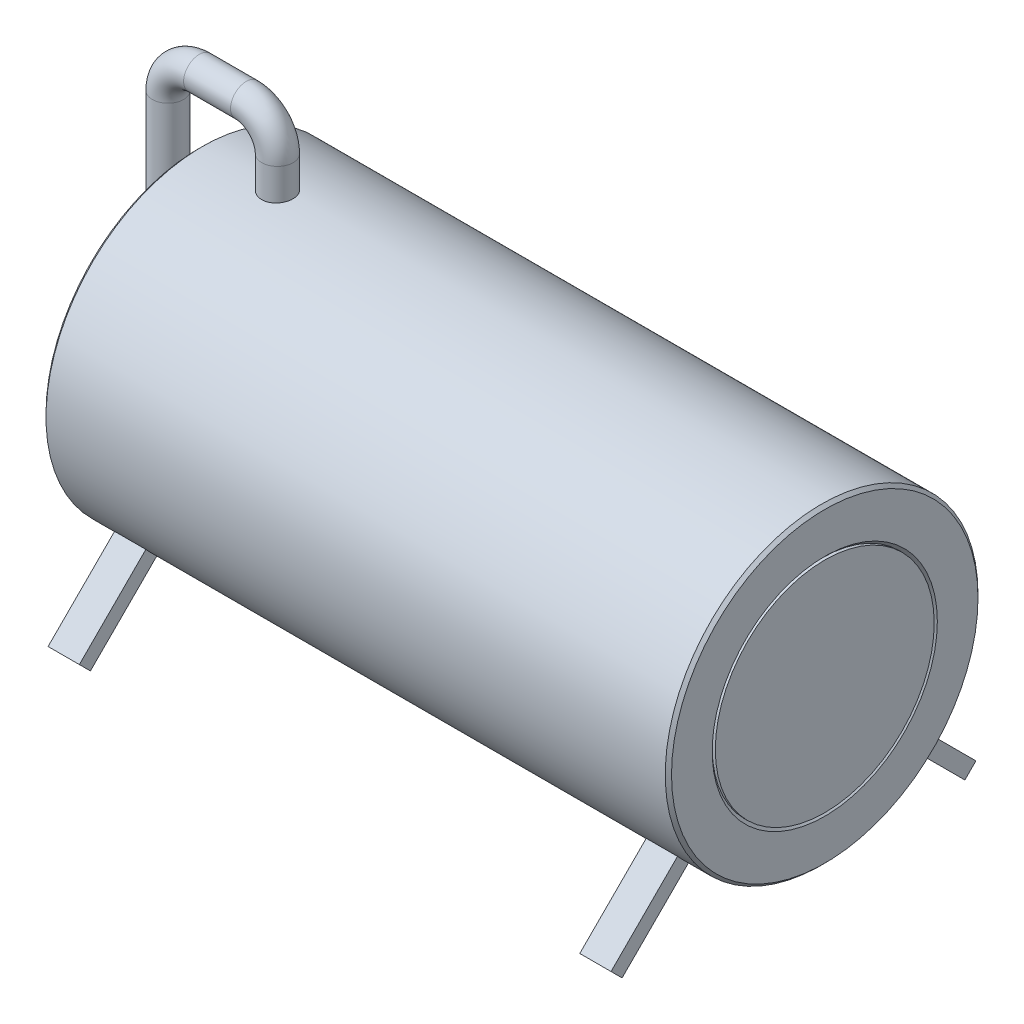
SolidWorks part; units mm, degrees
material "Aço galvanizado"
ref_plane "Plano frontal"
ref_plane "Plano superior" through (0, 0, 0) normal (0, 1, 0) x (1, 0, 0)
ref_plane "Plano direito" through (0, 0, 0) normal (1, 0, 0) x (0, 0, -1)
sketch "Esboço1" plane through (0, 0, 0) normal (1, 0, 0) x (0, 0, -1)
  circle A0 centre (0, 0) radius 50
  dimension "D1" = 100
extrude "Ressalto-extrusão1" add sketch "Esboço1" along normal blind 200
sketch "Esboço2" plane through (200, 0, 0) normal (1, 0, 0) x (0, 0, -1)
  circle A0 centre (0, 0) radius 35
  dimension "D1" = 70
extrude "Corte-extrusão1" cut sketch "Esboço2" against normal blind 200
sketch "Esboço3" plane through (0, 0, 0) normal (0, 0, 1) x (1, 0, 0)
  line L0 (200, 0) -> (0, 0) construction
  line L1 (200, -50) -> (200, 50) construction
  line L2 (0, 50) -> (0, -50) construction
  line L3 (5, 47.5) -> (195, 47.5)
  line L4 (5, 47.5) -> (5, 37.5)
  line L5 (5, 37.5) -> (195, 37.5)
  line L6 (195, 47.5) -> (195, 37.5)
  dimension "D1" = 75
  dimension "D2" = 95
  dimension "D3" = 5
  dimension "D4" = 5
revolve "Corte-Revolução1" cut sketch "Esboço3" angle 360 about L0
chamfer "Chanfro1" distance 1 angle 45 4 edges at (200, 0, -35) (200, 0, -50) (0, 0, -35) (0, 0, -50)
ref_plane "Plano1" through (10, 0, 0) normal (-1, 0, 0) x (0, 0, 1)
sketch "Esboço4" plane through (10, 0, 0) normal (-1, 0, 0) x (0, 0, 1)
  line L0 (0, 0) -> (0, -50) construction
  line L1 (0, 0) -> (-35.3553, -35.3553) construction
  line L2 (-37.0789, -33.5434) -> (-58.3363, -54.8008)
  line L3 (-58.3363, -54.8008) -> (-54.8008, -58.3363)
  line L4 (-54.8008, -58.3363) -> (-33.5434, -37.0789)
  circle A0 centre (0, 0) radius 50 construction
  arc A1 (-37.0789, -33.5434) -> (-33.5434, -37.0789) centre (0, 0) ccw
  dimension "D1" = 45
  dimension "D2" = 30
  dimension "D3" = 5
  dimension "D4" = 2.5
extrude "Ressalto-extrusão2" add sketch "Esboço4" against normal blind 10
ref_point "Ponto1"
ref_point "Ponto2"
ref_axis "Eixo1" through (200, 0, 0) along (-1, 0, 0)
pattern_circular "PadrãoCircular1" count 2 every 90 about axis through (200, 0, 0) along (-1, 0, 0) of "Ressalto-extrusão2"
pattern_linear "Padrão linear1" count 2 spacing 170 along (1, 0, 0) of "PadrãoCircular1"
ref_plane "Plano2" through (0, 50, 0) normal (0, 1, 0) x (-1, 0, 0)
hole_wizard "Broca de rosquear para tarraxa de M10x1.01" positions "Esboço7" profile "Esboço6" hole size "M10x1.0" standard "Métrico Ansi" end condition up to next
sketch "Esboço7" plane through (0, 50, 0) normal (0, 1, 0) x (-1, 0, 0)
  line L0 (-200, 0) -> (0, 0) construction
  point P0 (-25, 0)
  dimension "D1" = 25
sketch "Esboço6" plane through (25, 50, 0) normal (1, 0, 0) x (0, 0, 1)
  line L0 (0, 0) -> (0, 2.5)
  line L1 (0, 2.5) -> (4.5, 2.5)
  line L2 (4.5, 2.5) -> (4.5, 0)
  line L5 (4.5, 0) -> (0, 0)
  line L11 (0, -6.35) -> (0, 107.95) construction
  dimension "Thru Hole Dia." = 9
  dimension "Thru Hole Depth" = 2.5
sketch "Esboço8" plane through (0, 0, 0) normal (0, 0, 1) x (1, 0, 0)
  line L0 (25, 47.5) -> (25, 60)
  line L1 (15, 70) -> (0, 70)
  line L2 (-10, 60) -> (-10, 10)
  line L3 (0, 0) -> (100, 0)
  line L4 (200, 0) -> (0, 0) construction
  line L5 (0, 49) -> (0, -49) construction
  line L6 (20.5, 50) -> (1, 50) construction
  arc A0 (-10, 10) -> (0, 0) centre (0, 10) ccw
  arc A1 (0, 70) -> (-10, 60) centre (0, 60) ccw
  arc A2 (25, 60) -> (15, 70) centre (15, 60) ccw
  dimension "D1" = 10
  dimension "D2" = 47.5
  dimension "D3" = 25
  dimension "D4" = 20
  dimension "D5" = 10
  dimension "D6" = 100
ref_plane "Plano3" through (0, 47.5, 0) normal (0, 1, 0) x (-1, 0, 0)
sketch "Esboço9" plane through (0, 47.5, 0) normal (0, 1, 0) x (-1, 0, 0)
  circle A0 centre (-25, 0) radius 5
  circle A1 centre (-25, 0) radius 2.5
  dimension "D1" = 10
  dimension "D2" = 5
sweep "Varredura1" add profiles "Esboço9" path "Esboço8"
chamfer "Chanfro2" distance 2.5 angle 45 1 edges at (100, 0, 2.5)
sketch "Esboço10" plane through (0, 0, 0) normal (0, 0, 1) x (1, 0, 0)
  line L0 (200, 0) -> (200, 35)
  line L1 (200, 0) -> (0, 0) construction
  line L2 (200, 35) -> (195, 35)
  line L3 (195, 35) -> (195, 0)
  line L4 (195, 0) -> (200, 0)
  line L5 (200, -49) -> (200, 49) construction
  dimension "D1" = 5
  dimension "D2" = 35
revolve "Revolução1" add sketch "Esboço10" angle 360 about axis through (200, 0, 0) along (-1, 0, 0)
sketch "Esboço13" plane through (0, 47.5, 0) normal (0, 1, 0) x (-1, 0, 0)
  line L0 (-200, 0) -> (0, 0) construction
  line L1 (0, -49) -> (0, 49) construction
  circle A1 centre (-25, 0) radius 2.5
  dimension "D1" = 5
  dimension "D2" = 25
extrude "Ressalto-extrusão3" [suppressed] add sketch "Esboço13" along normal blind 2
sketch "Esboço14" plane through (0, 0, 0) normal (0, 0, 1) x (1, 0, 0)
  line L0 (0, 36) -> (0, -36) construction
  line L1 (0, 35) -> (5, 35)
  line L2 (0, 35) -> (0, 5)
  line L3 (0, 5) -> (5, 5)
  line L4 (5, 35) -> (5, 5)
  line L5 (200, 0) -> (0, 0) construction
  dimension "D1" = 5
  dimension "D2" = 35
  dimension "D3" = 5
revolve "Revolução2" add sketch "Esboço14" angle 360 about axis through (200, 0, 0) along (-1, 0, 0)
sketch "Sketch1" plane through (0, 0, 0) normal (0, 0, 1) x (1, 0, 0)
  line L0 (100, 0) -> (102.579, 0)
  line L4 (100, -5) -> (100, 5) construction
  line L5 (102.579, 0) -> (102.579, 7.5929)
  line L6 (102.579, 7.5929) -> (100, 7.5929)
  line L7 (100, 7.5929) -> (100, 0)
  line L8 (100, 0) -> (102.579, 0) construction
revolve "Revolve2" add sketch "Sketch1" angle 360 about L8
